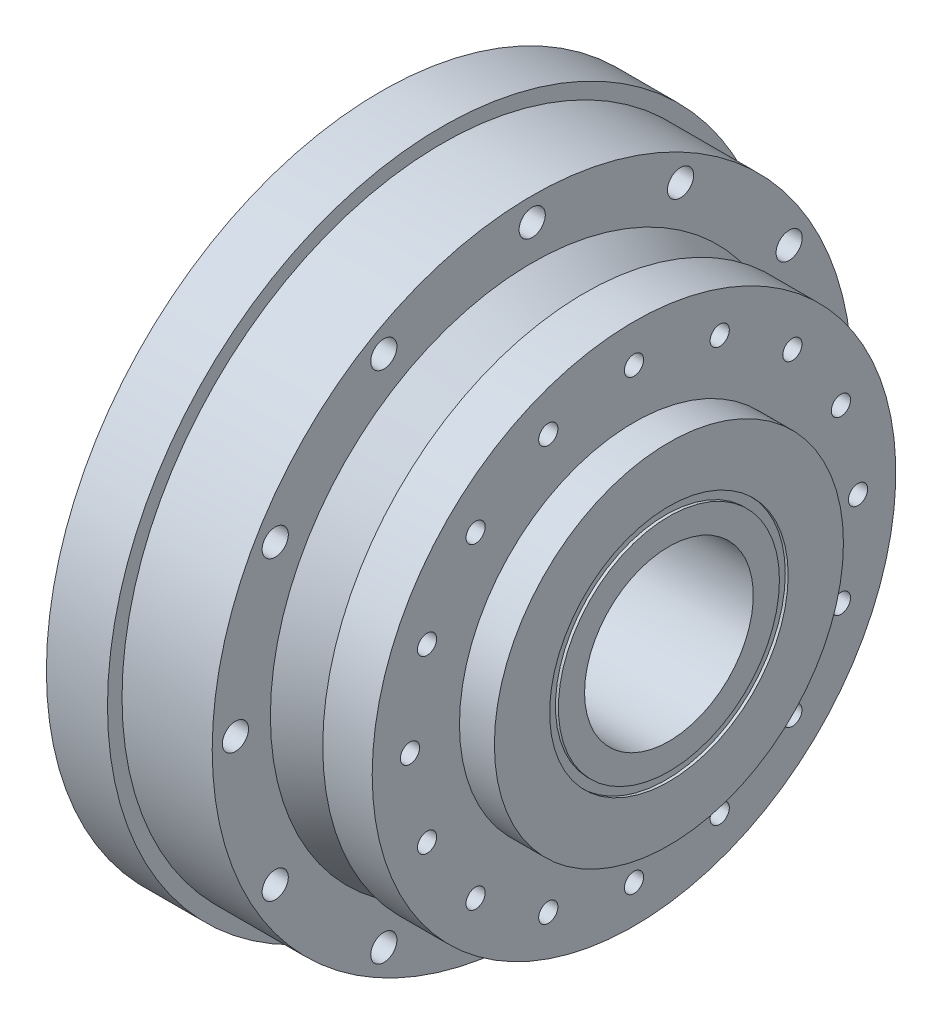
SolidWorks part; units mm, degrees
ref_plane "前视基准面" through (0, 0, 0) normal (0, 0, 1) x (1, 0, 0)
ref_plane "上视基准面" through (0, 0, 0) normal (0, 1, 0) x (1, 0, 0)
ref_plane "右视基准面" through (0, 0, 0) normal (1, 0, 0) x (0, 0, -1)
sketch "草图1" plane through (0, 0, 0) normal (0, 0, 1) x (1, 0, 0)
  line L0 (-65.2008, 0) -> (80.5899, 0) construction
  line L1 (0, 14.5) -> (0, 19)
  line L2 (0, 19) -> (6, 19)
  line L3 (6, 19) -> (6, 57.5)
  line L4 (6, 57.5) -> (16.5, 57.5)
  line L5 (16.5, 57.5) -> (16.5, 55)
  line L6 (16.5, 55) -> (32, 55)
  line L7 (32, 55) -> (32, 45)
  line L9 (41, 39.8038) -> (41, 45)
  line L10 (41, 45) -> (49.5, 45)
  line L11 (49.5, 45) -> (49.5, 30)
  line L12 (49.5, 30) -> (55.5, 30)
  line L13 (55.5, 30) -> (55.5, 14.5)
  line L14 (0, 14.5) -> (55.5, 14.5)
  line L15 (0, 0) -> (0, 43.251) construction
  line L17 (32, 45) -> (41, 39.8038)
  dimension "D1" = 115
  dimension "D2" = 38
  dimension "D3" = 29
  dimension "D4" = 110
  dimension "D5" = 90
  dimension "D6" = 60
  dimension "D7" = 6
  dimension "D8" = 10.5
  dimension "D9" = 26
  dimension "D10" = 55.5
  dimension "D11" = 8.5
  dimension "D12" = 6
  dimension "D13" = 60
revolve "旋转1" add sketch "草图1" angle 360 about L0
ref_axis "基准轴1" through (55.5, 0, 0) along (-1, 0, 0)
sketch "草图5" plane through (6, 0, 0) normal (-1, 0, 0) x (0, 0, 1)
  line L0 (0, 0) -> (0, 40.0957) construction
  circle A0 centre (0, 0) radius 51 construction
  circle A1 centre (0, 51) radius 2.25
  dimension "D1" = 102
  dimension "D2" = 4.5
extrude "切除-拉伸1" cut sketch "草图5" against normal up to next
pattern_circular "阵列(圆周)2" count 12 over 360 about axis through (55.5, 0, 0) along (-1, 0, 0) of "切除-拉伸1"
hole_wizard "M4 螺纹孔1" positions "草图16" profile "草图15" tap size "M4" standard "GB"
sketch "草图16" plane through (49.5, 0, 0) normal (1, 0, 0) x (0, 0, -1)
  line L0 (0, 0) -> (0, 44.049) construction
  circle A0 centre (0, 0) radius 38.5 construction
  point P0 (0, 38.5)
  dimension "D1" = 77
sketch "草图15" plane through (49.5, 38.5, 0) normal (0, 1, 0) x (0, 0, -1)
  line L0 (0, 0) -> (0, 16.4914)
  line L1 (0, 16.4914) -> (1.65, 15.5)
  line L2 (1.65, 15.5) -> (1.65, 0)
  line L5 (1.65, 0) -> (0, 0)
  line L10 (0, 16.4914) -> (-1.65, 15.5) construction
  line L11 (0, -6.35) -> (0, 107.95) construction
  dimension "螺纹孔钻头直径" = 3.3
  dimension "螺纹孔钻头深度" = 15.5
  dimension "导头角度" = 118
cosmetic thread "孔螺蚊线5" parameters "D1"=7, "D2"=4
pattern_circular "阵列(圆周)5" count 16 over 360 about axis through (55.5, 0, 0) along (-1, 0, 0) of "M4 螺纹孔1"
hole_wizard "M3 螺纹孔5" positions "草图18" profile "草图17" tap size "M3" standard "GB"
sketch "草图18" plane through (0, 0, 0) normal (-1, 0, 0) x (0, 0, 1)
  line L0 (0, 0) -> (0, 49.351) construction
  circle A0 centre (0, 0) radius 16.75 construction
  point P0 (0, 16.75)
  dimension "D1" = 33.5
sketch "草图17" plane through (0, 16.75, 0) normal (0, 1, 0) x (0, 0, 1)
  line L0 (0, 0) -> (0, 8.2511)
  line L1 (0, 8.2511) -> (1.25, 7.5)
  line L2 (1.25, 7.5) -> (1.25, 0)
  line L5 (1.25, 0) -> (0, 0)
  line L10 (0, 8.2511) -> (-1.25, 7.5) construction
  line L11 (0, -6.35) -> (0, 107.95) construction
  dimension "螺纹孔钻头直径" = 2.5
  dimension "螺纹孔钻头深度" = 7.5
  dimension "导头角度" = 118
cosmetic thread "孔螺蚊线7" parameters "D1"=6, "D2"=3
pattern_circular "阵列(圆周)6" count 6 over 360 about axis through (55.5, 0, 0) along (-1, 0, 0) of "M3 螺纹孔5"
sketch "草图19" plane through (6, 0, 0) normal (-1, 0, 0) x (0, 0, 1)
  circle A0 centre (0, 0) radius 19
  circle A1 centre (0, 0) radius 20.5
  dimension "D1" = 38
  dimension "D2" = 41
extrude "切除-拉伸6" cut sketch "草图19" against normal blind 0.5
sketch "草图20" plane through (55.5, 0, 0) normal (1, 0, 0) x (0, 0, -1)
  circle A0 centre (0, 0) radius 19
  circle A1 centre (0, 0) radius 20.5
  dimension "D1" = 38
  dimension "D2" = 41
extrude "切除-拉伸7" cut sketch "草图20" against normal blind 0.5
